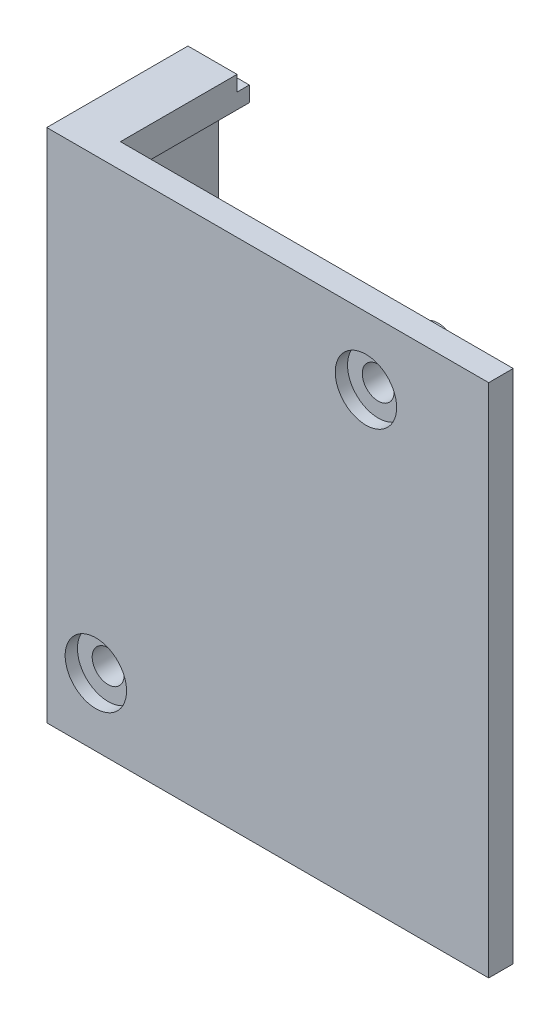
SolidWorks part; units mm, degrees
ref_plane "前视基准面" through (0, 0, 0) normal (0, 0, 1) x (1, 0, 0)
ref_plane "上视基准面" through (0, 0, 0) normal (0, 1, 0) x (1, 0, 0)
ref_plane "右视基准面" through (0, 0, 0) normal (1, 0, 0) x (0, 0, -1)
sketch "草图1" plane through (0, 0, 0) normal (0, 0, 1) x (1, 0, 0)
  line L1 (21, 21) -> (-15, 21)
  line L2 (21, 21) -> (21, -21)
  line L3 (21, -21) -> (-15, -21)
  line L4 (-15, 21) -> (-15, -21)
extrude "凸台-拉伸1" add sketch "草图1" along normal blind 2
sketch "草图2" plane through (0, 0, 0) normal (0, 0, -1) x (-1, 0, 0)
  line L0 (15, -21) -> (-21, -21) construction
  line L1 (15, 21) -> (11, 21)
  line L2 (15, 21) -> (15, -21)
  line L3 (15, -21) -> (11, -21)
  line L4 (11, 21) -> (11, -21)
  line L5 (11, -19.75) -> (11, -21) construction
  line L6 (11, 18.5) -> (11, -18.5)
  line L7 (11, 18.5) -> (13.5, 18.5)
  line L8 (11, -18.5) -> (13.5, -18.5)
  line L9 (13.5, 18.5) -> (13.5, -18.5)
  line L10 (13, 16.5) -> (13, -16.5) construction
  line L11 (11, 19.75) -> (11, -19.75)
  line L12 (11, 19.75) -> (14, 19.75)
  line L13 (11, -19.75) -> (14, -19.75)
  line L14 (14, 19.75) -> (14, -19.75)
  line L15 (13.5, 18.5) -> (11, -18.5) construction
  point P17 (12.25, 0)
  line M4 (-21, -21) -> (15, -21)
  line M5 (15, -21) -> (15, 21)
  line M6 (15, 21) -> (-21, 21)
  dimension "D1" = 0.5
  dimension "D2" = 0.5
extrude "凸台-拉伸2" add sketch "草图2" along normal blind 9.5 contours L12 L14 L13 L4 M4 M5 M6 | L14 L12 L4 L7 L9 L8 L13 region at (-14.197, 0, 0) region at (-12.5, 19.3539, 0)
extrude "凸台-拉伸3" add sketch "草图2<3>" along normal blind 10.5 contours L14 L12 L4 L7 L9 L8 L13 region at (-12.5, 19.3539, 0)
sketch "草图2<3>" plane through (0, 0, 0) normal (0, 0, -1) x (-1, 0, 0) same geometry as "草图2"
sketch "草图3" plane through (-13.5, 0, 0) normal (1, 0, 0) x (0, 0, -1)
  line L0 (3.95, -3.4) -> (3.95, 3.4) construction
  line L1 (3.95, -16.4) -> (3.95, 16.4) construction
  line L2 (2.35, -3.4) -> (2.35, 3.4)
  line L3 (5.55, -3.4) -> (5.55, 3.4)
  arc A0 (2.35, -3.4) -> (5.55, -3.4) centre (3.95, -3.4) ccw
  arc A1 (5.55, 3.4) -> (2.35, 3.4) centre (3.95, 3.4) ccw
  point P4 (3.95, 0)
  point P9 (3.95, -5)
  point P10 (3.95, 5)
  point P11 (0, 0)
  dimension "D1" = 10
  dimension "D2" = 3.2
extrude "切除-拉伸1" cut sketch "草图3" against normal up to next
sketch "草图4" plane through (0, 0, 0) normal (0, 0, -1) x (-1, 0, 0)
  circle A0 centre (11, -15.5) radius 1.3
  circle A1 centre (11, -15.5) radius 1.75
  circle A2 centre (-11, 15.5) radius 1.3
  circle A3 centre (-11, 15.5) radius 1.75
  dimension "D1" = 3.5
  dimension "D2" = 2.6
extrude "凸台-拉伸4" add sketch "草图4" along normal blind 3.9
extrude "切除-拉伸2" cut sketch "草图4<2>" against normal up to next contours A2 | A0
sketch "草图4<2>" plane through (0, 0, 0) normal (0, 0, -1) x (-1, 0, 0) same geometry as "草图4"
sketch "草图5" plane through (0, 0, 2) normal (0, 0, 1) x (1, 0, 0)
  circle A0 centre (11, 15.5) radius 2.5
  circle A1 centre (-11, -15.5) radius 2.5
  dimension "D1" = 5
extrude "切除-拉伸3" cut sketch "草图5" against normal blind 1
sketch "草图6" plane through (0, 0, 0) normal (0, 0, -1) x (-1, 0, 0)
  line L0 (-8.95, 0.8) -> (-7.35, -0.8) construction
  circle A0 centre (-8.15, 0) radius 2
  point P6 (0, 0)
  point P7 (0, 0)
  point P8 (-9.4974, 0.0965)
  point P9 (-8.15, 0)
  dimension "D1" = 4
extrude "切除-拉伸4" cut sketch "草图6" against normal blind 1.5
